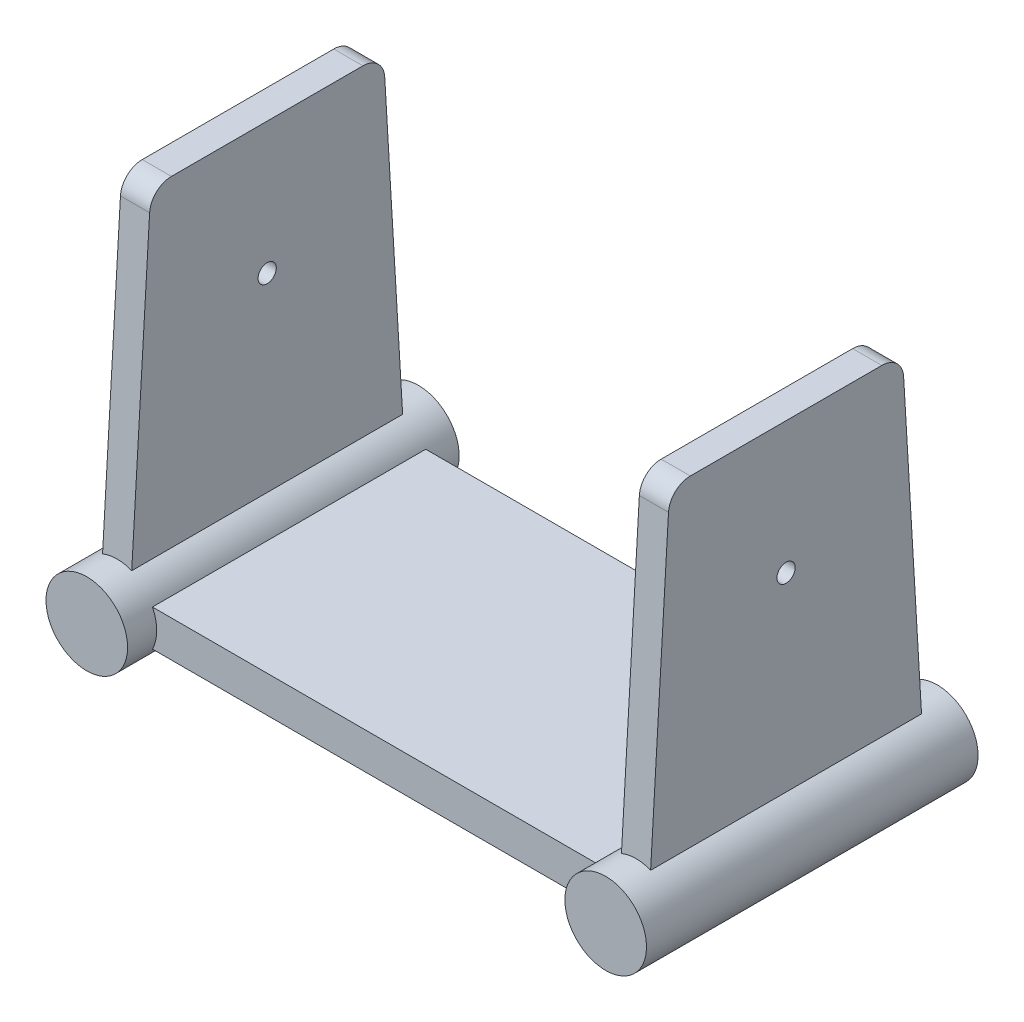
SolidWorks part; units mm, degrees
ref_plane "Front" through (0, 0, 0) normal (0, 0, 1) x (1, 0, 0)
ref_plane "Top" through (0, 0, 0) normal (0, 1, 0) x (1, 0, 0)
ref_plane "Right" through (0, 0, 0) normal (1, 0, 0) x (0, 0, -1)
sketch "Sketch2" plane through (0, 0, 0) normal (0, 1, 0) x (1, 0, 0)
  line L1 (-71.1742, -37.4834) -> (71.1742, -37.4834)
  line L2 (-71.1742, -37.4834) -> (-71.1742, 37.4834)
  line L3 (-71.1742, 37.4834) -> (71.1742, 37.4834)
  line L4 (71.1742, -37.4834) -> (71.1742, 37.4834)
  line L5 (-71.1742, -37.4834) -> (71.1742, 37.4834) construction
  line L6 (-71.1742, 37.4834) -> (71.1742, -37.4834) construction
  point P0 (0, 0)
extrude "Boss-Extrude1" add sketch "Sketch2" along normal blind 10
sketch "Sketch3" plane through (0, 0, 37.4834) normal (0, 0, 1) x (1, 0, 0)
  line L0 (-71.1742, 10) -> (-71.1742, 0) construction
  line L1 (0, 0) -> (0, 10) construction
  line L2 (-71.1742, 0) -> (71.1742, 0) construction
  line L3 (-71.1742, 10) -> (71.1742, 10) construction
  circle A0 centre (-71.1742, 5) radius 11.1899
  circle A1 centre (71.1742, 5) radius 11.1899
extrude "Boss-Extrude3" add sketch "Sketch3<2>" along normal blind 8
sketch "Sketch3<2>" plane through (0, 0, 37.4834) normal (0, 0, 1) x (1, 0, 0) same geometry as "Sketch3"
sketch "Sketch6" plane through (-71.1742, 0, 0) normal (-1, 0, 0) x (0, 0, 1)
  line L1 (31.9158, 103.6896) -> (37.4834, 10)
  line L4 (37.4834, 10) -> (37.4834, 0)
  line L5 (0, 10) -> (0, 103.6896) construction
  line L6 (37.4834, 0) -> (-37.4834, 0)
  line L7 (-31.9158, 103.6896) -> (0, 103.6896)
  line L8 (0, 103.6896) -> (31.9158, 103.6896)
  line L9 (-37.4834, 0) -> (37.4834, 0) construction
  line L10 (-37.4834, 0) -> (-37.4834, 10)
  line L11 (-37.4834, 10) -> (-31.9158, 103.6896)
  circle A0 centre (0, 67.5632) radius 2.5
  dimension "D1" = 5
extrude "Boss-Extrude5" add sketch "Sketch6" along normal mid plane 8
extrude "Boss-Extrude2" add sketch "Sketch3" against normal up to surface (74.9668 mm away) up to face at (-15.0348, 6, -37.4834)
sketch "Sketch4" plane through (0, 0, -37.4834) normal (0, 0, -1) x (-1, 0, 0)
  circle A0 centre (-71.1742, 5) radius 11.1899
  circle A1 centre (71.1742, 5) radius 11.1899
  arc A2 (61.1636, 0) -> (61.1636, 10) centre (71.1742, 5) ccw construction
  arc A3 (-61.1636, 10) -> (-61.1636, 0) centre (-71.1742, 5) ccw construction
extrude "Boss-Extrude4" add sketch "Sketch4" along normal blind 8
mirror "Mirror1" about plane through (0, 0, 0) normal (1, 0, 0) of "Boss-Extrude5"
fillet "Fillet1" radius 6 4 edges at (71.1742, 103.6896, -31.9158) (71.1742, 103.6896, 31.9158) (-71.1742, 103.6896, 31.9158) (-71.1742, 103.6896, -31.9158)
sketch "Sketch8" plane through (0, 0, 0) normal (1, 0, 0) x (0, 0, -1)
  line L0 (-24.6693, 0) -> (0, 0)
  line L1 (0, 0) -> (24.6693, 0)
  line L2 (0, 0) -> (0, 15.5195) construction
  line L3 (0, 0) -> (0, -22.6029) construction
  arc A0 (-24.6693, 0) -> (24.6693, 0) centre (0, 2.1609) ccw
  circle A1 centre (0, -11.5171) radius 4.1675
extrude "Boss-Extrude6" add sketch "Sketch8" along normal mid plane 62
sketch "Sketch9" plane through (0, 0, 0) normal (0, 0, 1) x (1, 0, 0)
  line L0 (-31, 0) -> (-23, 0) construction
  line L1 (0, 0) -> (-23, 0)
  line L2 (-67.1742, 98.0455) -> (-75.1742, 98.0455) construction
  line L3 (-2.1107, -24.6018) -> (-23, -24.6018)
  line L4 (-23, 0) -> (-23, -24.6018)
  line L5 (0, 0) -> (23, 0)
  line L7 (-2.1107, -24.6018) -> (23, -24.6018)
  line L8 (23, 0) -> (23, -24.6018)
extrude "Cut-Extrude1" cut sketch "Sketch9" against normal mid plane 62 contours L3 L4 L1 L5 L8 L7
